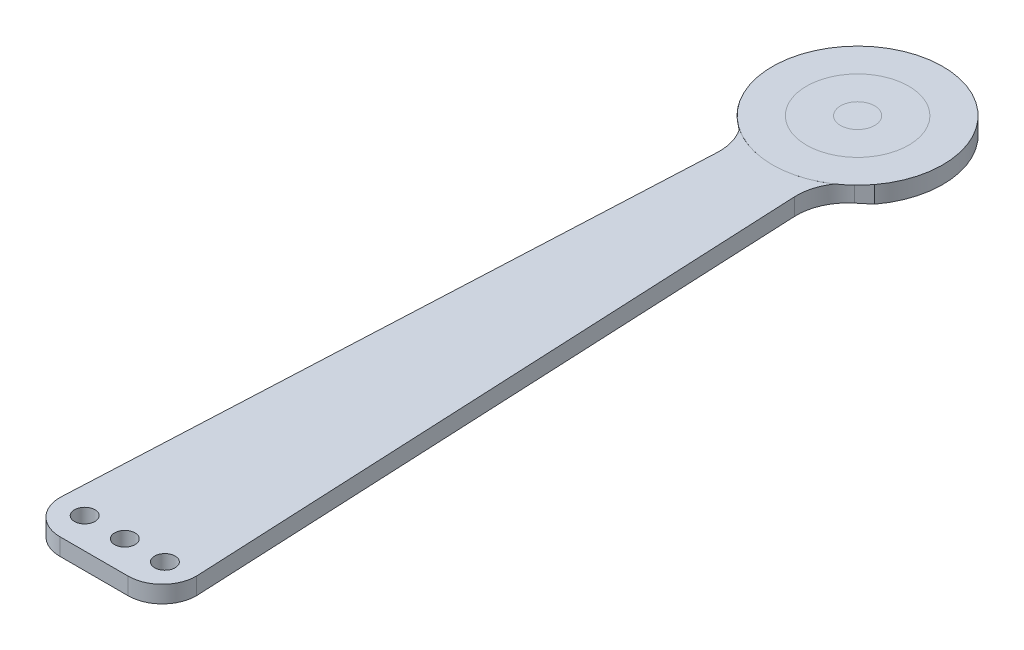
SolidWorks part; units mm, degrees
ref_plane "Front Plane" through (0, 0, 0) normal (0, 0, 1) x (1, 0, 0)
ref_plane "Top Plane" through (0, 0, 0) normal (0, 1, 0) x (1, 0, 0)
ref_plane "Right Plane" through (0, 0, 0) normal (1, 0, 0) x (0, 0, -1)
sketch "Sketch2" plane through (0, 0, 0) normal (0, 1, 0) x (1, 0, 0)
  circle A0 centre (0, 0) radius 25
  point P3 (0, 0)
  dimension "D1" = 50
extrude "Boss-Extrude2" add sketch "Sketch2" along normal blind 5 contours A0
sketch "Sketch3" plane through (0, 5, 0) normal (0, 1, 0) x (1, 0, 0)
  circle A0 centre (0, 0) radius 5
  circle A1 centre (0, 0) radius 15
extrude "Boss-Extrude3" add sketch "Sketch3" along normal blind 0.0001 contours A1
sketch "Sketch4" plane through (0, 5.0001, 0) normal (0, 1, 0) x (1, 0, 0)
  circle A0 centre (0, 0) radius 5
extrude "Boss-Extrude4" add sketch "Sketch4" along normal blind 0.0001
sketch "Sketch20" plane through (0, 0, 0) normal (0, 1, 0) x (1, 0, 0)
  line L0 (0, 0) -> (20, 0)
  line L1 (0, 0) -> (-20, 0)
  line L3 (-20, 0) -> (20, 0)
  line L4 (-20, 0) -> (-20, -224)
  line L5 (-20, -224) -> (20, -224)
  line L6 (20, 0) -> (20, -224)
  circle A0 centre (0, -215) radius 3
  circle A1 centre (11.77, -215) radius 3
  circle A3 centre (-11.77, -215) radius 3
  dimension "D4" = 11.77
  dimension "D5" = 215
  dimension "D6" = 6
  dimension "D7" = 2
  dimension "D1" = 20
  dimension "D2" = 20
  dimension "D3" = 224
extrude "Boss-Extrude8" add sketch "Sketch20" along normal blind 4.9999 contours L6 L0 L1 L4 L5 A3 A1 A0 region at (0, 0, 111.0156)
fillet "Fillet6" radius 10 2 edges at (-20, 2.5, 224) (20, 2.5, 224)
sketch "Sketch21" plane through (0, 4.9999, 0) normal (0, 1, 0) x (1, 0, 0)
  line L0 (20, -214) -> (11.0051, -22.4475)
  line L1 (11.0051, -22.4475) -> (20, -15)
  line L2 (20, -15) -> (20, -214)
  line L3 (-20, -214) -> (-10.8908, -22.5031)
  line L4 (-10.8908, -22.5031) -> (-20, -15)
  line L5 (-20, -15) -> (-20, -214)
  circle A0 centre (0, 0) radius 25 construction
  arc A1 (-20, -15) -> (20, -15) centre (0, 0) ccw construction
  point P10 (0, 0)
  point P13 (11.0051, -22.4475)
  point P17 (-10.8908, -22.4475)
extrude "Cut-Extrude4" cut sketch "Sketch21" against normal blind 4.9999
fillet "Fillet8" radius 15 2 edges at (-10.8908, 2.5, 22.5031) (11.0051, 2.5, 22.4475)
